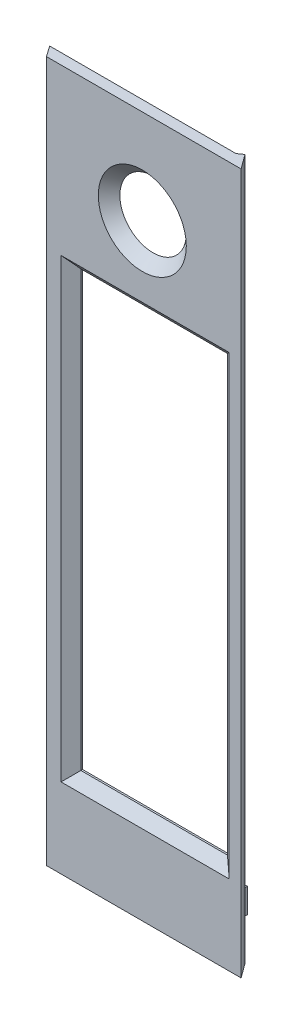
SolidWorks part; units mm, degrees
ref_plane "前视基准面" through (0, 0, 0) normal (0, 0, 1) x (1, 0, 0)
ref_plane "上视基准面" through (0, 0, 0) normal (0, 1, 0) x (1, 0, 0)
ref_plane "右视基准面" through (0, 0, 0) normal (1, 0, 0) x (0, 0, -1)
other "Configuration Table"
sketch "草图1" plane through (0, 0, 0) normal (0, 0, 1) x (1, 0, 0)
  line L2 (-39.759, 32.5) -> (-22.481, 32.5)
  line L3 (-39.759, 32.5) -> (-39.759, -32.5)
  line L4 (-39.759, -32.5) -> (-22.481, -32.5)
  line L5 (-22.481, 32.5) -> (-22.481, -32.5)
  line L6 (-36.7043, 16.2) -> (-23.1043, 16.2)
  line L7 (-36.7043, 16.2) -> (-36.7043, -24.1)
  line L8 (-36.7043, -24.1) -> (-23.1043, -24.1)
  line L9 (-23.1043, 16.2) -> (-23.1043, -24.1)
  circle A0 centre (-30.1677, 23.76) radius 3.082
  dimension "D1" = 40.3
  dimension "D2" = 16.3
  dimension "D3" = 13.6
extrude "凸台-拉伸1" add sketch "草图1" along normal blind 1
sketch "草图2" plane through (0, 0, 0) normal (0, 0, -1) x (-1, 0, 0)
  line L0 (36.2677, 24.6976) -> (36.2677, 27.7216)
  line L1 (36.2677, -26.5) -> (36.2677, 28.06) construction
  line L2 (36.2677, 27.7216) -> (34.9293, 29.06)
  line L3 (35.2677, 29.06) -> (25.3677, 29.06) construction
  line L4 (34.9293, 29.06) -> (31.366, 29.06)
  line L5 (31.366, 29.06) -> (31.366, 28.3185)
  line L6 (31.366, 28.3185) -> (35.2677, 24.6976)
  line L7 (35.2677, 24.6976) -> (36.2677, 24.6976)
  line L8 (28.8258, 29.06) -> (26.3916, 29.06)
  line L9 (26.3916, 29.06) -> (24.3677, 27.036)
  line L10 (24.3677, 28.06) -> (24.3677, 18.46) construction
  line L11 (24.3677, 27.036) -> (24.3677, 24.9699)
  line L12 (24.3677, 24.9699) -> (25.4773, 24.9699)
  line L13 (25.4773, 24.9699) -> (28.8258, 28.3185)
  line L14 (28.8258, 28.3185) -> (28.8258, 29.06)
  line L16 (34.5713, -29.9151) -> (23.2046, -29.9151)
  line L17 (34.5713, -29.9151) -> (34.5713, -27.6352)
  line L18 (34.5713, -27.6352) -> (23.2046, -27.6352)
  line L19 (23.2046, -29.9151) -> (23.2046, -27.6352)
extrude "凸台-拉伸2" add sketch "草图2" along normal blind 1.8
sketch "草图3" plane through (0, -32.5, 0) normal (0, -1, 0) x (1, 0, 0)
  line L0 (-22.481, 1) -> (-20.9972, 1)
  line L1 (-20.9972, 1) -> (-21.7391, 0)
  line L2 (-21.7391, 0) -> (-22.481, 0)
  line L3 (-22.481, 0) -> (-22.481, 1)
extrude "凸台-拉伸3" add sketch "草图3" against normal up to surface (65 mm away) up to face at (-31.12, 32.5, 0.5)
sketch "草图4" plane through (0, -32.5, 0) normal (0, -1, 0) x (1, 0, 0)
  line L1 (-40.3821, -0.8899) -> (-38.6479, 1.5868) construction
  line L8 (-40.9576, -1.7118) -> (-39.759, 0) construction
  line L9 (-39.759, 0) -> (-39.0588, 1)
  line L10 (-39.759, 1) -> (-20.9972, 1) construction
  line L11 (-39.0588, 1) -> (-39.759, 1)
  line L12 (-39.759, 1) -> (-39.759, 0)
extrude "切除-拉伸1" cut sketch "草图4" against normal up to surface (65 mm away) up to face at (-30.5636, 32.5, 0.5)
sketch "草图5" plane through (0, -32.5, 0) normal (0, -1, 0) x (1, 0, 0)
  line L0 (-21.7391, 0) -> (-21.9832, -0.3486)
  line L1 (-21.2387, -0.8699) -> (-22.481, 0) construction
  line L2 (-21.9832, -0.3486) -> (-22.481, 0)
  line L3 (-39.759, 0) -> (-21.7391, 0) construction
  line L4 (-22.481, 0) -> (-21.7391, 0)
extrude "凸台-拉伸4" add sketch "草图5" against normal up to surface (65 mm away) up to face at (-30.3885, 32.5, 0.5)
chamfer "倒角1" distance 1 angle 45 1 edges at (-27.0856, 23.76, 1)
chamfer "倒角2" distance 1 angle 40 4 edges at (-29.9043, 16.2, 1) (-36.7043, -3.95, 1) (-23.1043, -3.95, 1) (-29.9043, -24.1, 1) first distance on face at (-26.0856, 23.76, 1)
